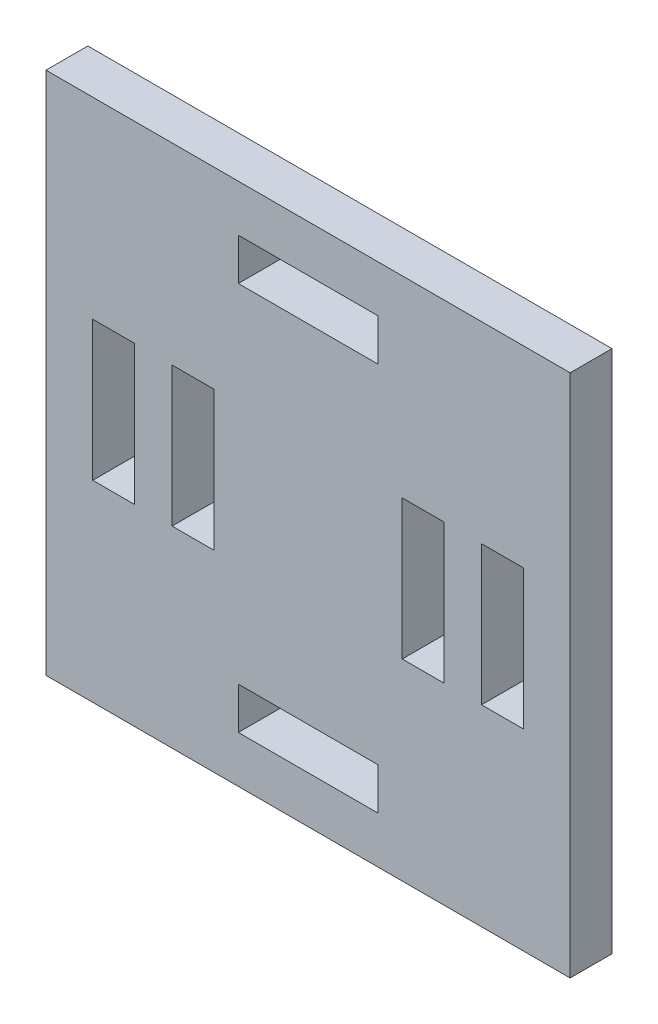
SolidWorks part; units mm, degrees
ref_plane "Front Plane" through (0, 0, 0) normal (0, 0, 1) x (1, 0, 0)
ref_plane "Top Plane" through (0, 0, 0) normal (0, 1, 0) x (1, 0, 0)
ref_plane "Right Plane" through (0, 0, 0) normal (1, 0, 0) x (0, 0, -1)
sketch "Sketch1" plane through (0, 0, 0) normal (0, 0, 1) x (1, 0, 0)
  line L0 (-18.785, -18.785) -> (-18.785, 18.785)
  line L1 (-18.785, 18.785) -> (18.785, 18.785)
  line L2 (18.785, -18.785) -> (-18.785, -18.785)
  line L3 (18.785, 18.785) -> (18.785, -18.785)
  line L4 (-1.5, -15.785) -> (1.5, -15.785)
  line L5 (1.5, -15.785) -> (1.5, -12.785)
  line L6 (-1.5, -12.785) -> (-1.5, -15.785)
  line L7 (1.5, -12.785) -> (-1.5, -12.785)
  line L8 (15.785, -1.5) -> (15.785, 1.5)
  line L9 (15.785, 1.5) -> (12.785, 1.5)
  line L10 (12.785, -1.5) -> (15.785, -1.5)
  line L11 (12.785, 1.5) -> (12.785, -1.5)
  line L12 (-15.785, 1.5) -> (-15.785, -1.5)
  line L13 (-15.785, -1.5) -> (-12.785, -1.5)
  line L14 (-12.785, 1.5) -> (-15.785, 1.5)
  line L15 (-12.785, -1.5) -> (-12.785, 1.5)
  line L16 (-6.75, -2.5) -> (-6.75, 2.5)
  line L17 (-6.75, 2.5) -> (-9.75, 2.5)
  line L18 (-9.75, 2.5) -> (-9.75, -2.5)
  line L19 (-9.75, -2.5) -> (-6.75, -2.5)
  line L20 (1.5, 15.785) -> (-1.5, 15.785)
  line L21 (-1.5, 15.785) -> (-1.5, 12.785)
  line L22 (1.5, 12.785) -> (1.5, 15.785)
  line L23 (-1.5, 12.785) -> (1.5, 12.785)
  line L24 (9.75, -2.5) -> (9.75, 2.5)
  line L25 (6.75, -2.5) -> (9.75, -2.5)
  line L26 (9.75, 2.5) -> (6.75, 2.5)
  line L27 (6.75, 2.5) -> (6.75, -2.5)
extrude "Plate_thickness_3mm" add sketch "Sketch1" along normal blind 3
sketch "草图1" plane through (0, 0, 3) normal (0, 0, 1) x (1, 0, 0)
  line L0 (-15.785, -1.5) -> (-12.785, -1.5) construction
  line L1 (-1.5, 12.785) -> (1.5, 12.785)
  line L2 (-1.5, 12.785) -> (-1.5, 12.435)
  line L3 (-1.5, 12.435) -> (1.5, 12.435)
  line L4 (1.5, 12.785) -> (1.5, 12.435)
  line L5 (-12.785, 1.5) -> (-12.435, 1.5)
  line L6 (-12.785, 1.5) -> (-12.785, -1.5269)
  line L7 (-12.785, -1.5269) -> (-12.435, -1.5269)
  line L8 (-12.435, 1.5) -> (-12.435, -1.5269)
  line L9 (12.785, 1.5) -> (12.435, 1.5)
  line L10 (12.785, 1.5) -> (12.785, -1.5269)
  line L11 (12.785, -1.5269) -> (12.435, -1.5269)
  line L12 (12.435, 1.5) -> (12.435, -1.5269)
  line L13 (-1.5, -12.785) -> (1.5, -12.785)
  line L14 (-1.5, -12.785) -> (-1.5, -12.435)
  line L15 (-1.5, -12.435) -> (1.5, -12.435)
  line L16 (1.5, -12.785) -> (1.5, -12.435)
  line L17 (-15.785, 1.5) -> (-15.435, 1.5)
  line L18 (-15.785, 1.5) -> (-15.785, -1.5)
  line L19 (-15.785, -1.5) -> (-15.435, -1.5)
  line L20 (-15.435, 1.5) -> (-15.435, -1.5)
  line L21 (1.5, 12.785) -> (1.5, 15.785) construction
  line L22 (-1.5, 15.785) -> (1.5, 15.785)
  line L23 (-1.5, 15.785) -> (-1.5, 15.435)
  line L24 (-1.5, 15.435) -> (1.5, 15.435)
  line L25 (1.5, 15.785) -> (1.5, 15.435)
  line L26 (12.785, -1.5) -> (15.785, -1.5) construction
  line L27 (15.785, 1.5) -> (15.435, 1.5)
  line L28 (15.785, 1.5) -> (15.785, -1.5)
  line L29 (15.785, -1.5) -> (15.435, -1.5)
  line L30 (15.435, 1.5) -> (15.435, -1.5)
  line L31 (1.5, -15.785) -> (1.5, -12.785) construction
  line L32 (-1.5, -15.785) -> (1.5, -15.785)
  line L33 (-1.5, -15.785) -> (-1.5, -15.435)
  line L34 (-1.5, -15.435) -> (1.5, -15.435)
  line L35 (1.5, -15.785) -> (1.5, -15.435)
  dimension "D1" = 0.35
  dimension "D2" = 0.35
  dimension "D3" = 0.35
  dimension "D4" = 0.35
  dimension "D5" = 0.35
  dimension "D6" = 0.35
  dimension "D7" = 0.35
  dimension "D8" = 0.35
extrude "切除-拉伸1" cut sketch "草图1" against normal up to surface (3 mm away) up to face at (0, 0, 0)
extrude "凸台-拉伸1" add sketch "草图1<2>" against normal up to surface (3 mm away) contours L22 L25 L24 L23 | L18 L19 L20 L17 | L28 L29 L30 L27 | L34 L35 L32 L33 up to face at (0, -14.11, 0)
sketch "草图1<2>" plane through (0, 0, 3) normal (0, 0, 1) x (1, 0, 0) same geometry as "草图1"
sketch "草图2" plane through (0, 0, 3) normal (0, 0, 1) x (1, 0, 0)
  line L0 (-18.785, 0) -> (18.785, 0)
  line L1 (-18.785, 18.785) -> (-18.785, -18.785) construction
  line L2 (18.785, -18.785) -> (18.785, 18.785) construction
  line L3 (0, 18.785) -> (0, -18.785)
  line L4 (18.785, 18.785) -> (-18.785, 18.785) construction
  line L5 (-18.785, -18.785) -> (18.785, -18.785) construction
  line L6 (15.435, -5) -> (12.435, -5)
  line L7 (-15.435, 5) -> (-12.435, 5)
  line L8 (-15.435, 5) -> (-15.435, -5)
  line L9 (-15.435, -5) -> (-12.435, -5)
  line L10 (-12.435, 5) -> (-12.435, -5)
  line L11 (-15.435, 5) -> (-12.435, -5) construction
  line L12 (-15.435, -5) -> (-12.435, 5) construction
  line L13 (-5, -12.435) -> (5, -12.435)
  line L14 (-5, -12.435) -> (-5, -15.435)
  line L15 (-5, -15.435) -> (5, -15.435)
  line L16 (5, -12.435) -> (5, -15.435)
  line L17 (-5, -12.435) -> (5, -15.435) construction
  line L18 (-5, -15.435) -> (5, -12.435) construction
  line L19 (12.435, 5) -> (12.435, -5)
  line L20 (15.435, 5) -> (12.435, 5)
  line L21 (15.435, 5) -> (15.435, -5)
  line L22 (-5, 15.435) -> (5, 15.435)
  line L23 (5, 12.435) -> (5, 15.435)
  line L24 (-5, 12.435) -> (5, 12.435)
  line L25 (-5, 12.435) -> (-5, 15.435)
  line L27 (9.75, -5) -> (6.75, -5)
  line L28 (-9.75, 5) -> (-6.75, 5)
  line L29 (-9.75, 5) -> (-9.75, -5)
  line L30 (-9.75, -5) -> (-6.75, -5)
  line L31 (-6.75, 5) -> (-6.75, -5)
  line L32 (-9.75, 5) -> (-6.75, -5) construction
  line L33 (-9.75, -5) -> (-6.75, 5) construction
  line L34 (6.75, 5) -> (6.75, -5)
  line L35 (9.75, 5) -> (6.75, 5)
  line L36 (9.75, 5) -> (9.75, -5)
  point P12 (-13.935, 0)
  point P17 (0, -13.935)
  point P33 (-8.25, 0)
  line M16 (-1.5, -15.435) -> (-1.5, -12.435)
  line M18 (1.5, -12.435) -> (1.5, -15.435)
  line M20 (15.435, -1.5) -> (12.785, -1.5)
  line M21 (12.785, -1.5) -> (12.785, -1.5269)
  line M22 (12.785, -1.5269) -> (12.435, -1.5269)
  line M24 (12.435, 1.5) -> (15.435, 1.5)
  line M26 (-15.435, 1.5) -> (-12.435, 1.5)
  line M28 (-12.435, -1.5269) -> (-12.785, -1.5269)
  line M29 (-12.785, -1.5269) -> (-12.785, -1.5)
  line M30 (-12.785, -1.5) -> (-15.435, -1.5)
  line M32 (1.5, 15.435) -> (1.5, 12.435)
  line M34 (-1.5, 12.435) -> (-1.5, 15.435)
  line M39 (-6.75, -2.5) -> (-9.75, -2.5)
  line M41 (-9.75, 2.5) -> (-6.75, 2.5)
  line M43 (9.75, -2.5) -> (6.75, -2.5)
  line M45 (6.75, 2.5) -> (9.75, 2.5)
  dimension "D1" = 10
  dimension "D2" = 10
extrude "切除-拉伸2" cut sketch "草图2" against normal up to surface (3 mm away) contours L10 L7 L8 M26 | L31 L28 L29 M41 | L31 L29 L30 M39 | L10 L8 L9 M28 M29 M30 | L25 L24 L22 M34 | L24 L23 L22 M32 | L36 L35 L34 M45 | L21 L20 L19 M24 | L21 L19 L6 M20 M21 M22 | L36 L34 L27 M43 | L16 L13 L15 M18 | L14 L15 L13 M16 region at (-13.935, 3.25, 3) region at (-13.9362, -3.2516, 3) region at (-8.25, 3.75, 3) region at (-8.25, -3.75, 3) region at (8.25, 3.75, 3) region at (8.25, -3.75, 3) region at (-3.25, 13.935, 3) region at (3.25, 13.935, 3) region at (-3.25, -13.935, 3) region at (3.25, -13.935, 3) region at (13.935, 3.25, 3) region at (13.9362, -3.2516, 3) up to face at (0, -13.935, 0)
